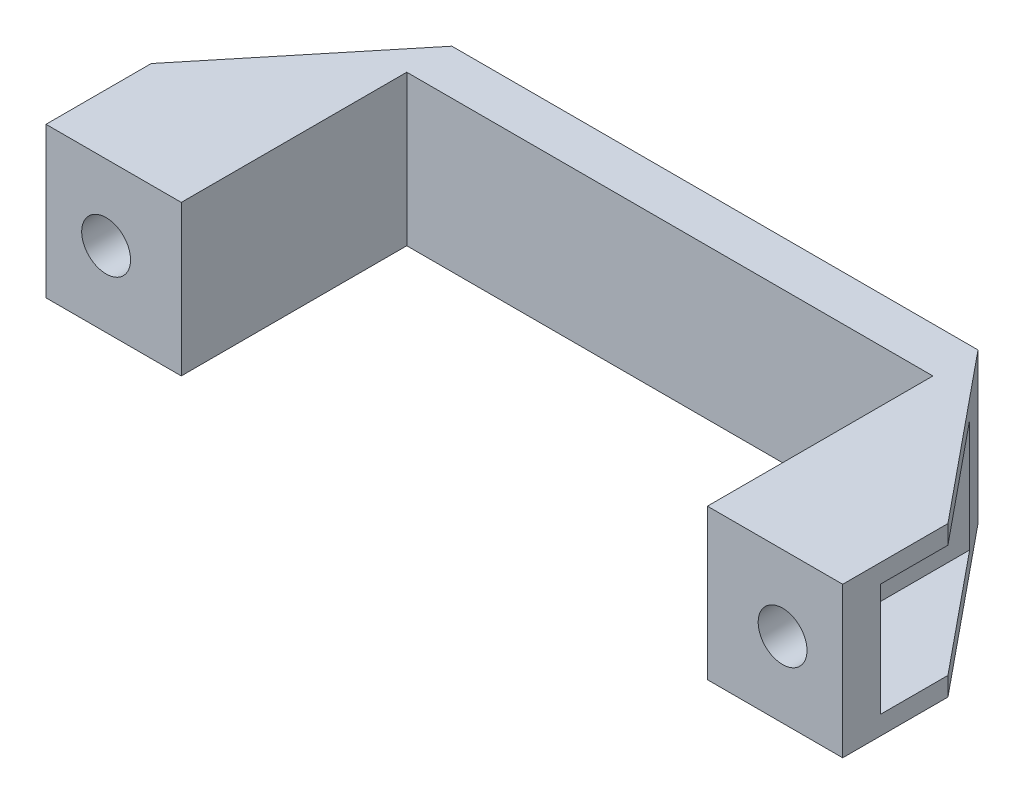
SolidWorks part; units mm, degrees
material "6061 合金"
ref_plane "前视基准面" through (0, 0, 0) normal (0, 0, 1) x (1, 0, 0)
ref_plane "上视基准面" through (0, 0, 0) normal (0, 1, 0) x (1, 0, 0)
ref_plane "右视基准面" through (0, 0, 0) normal (1, 0, 0) x (0, 0, -1)
ref_axis "X" through (88.99, 0, 0) along (-1, 0, 0)
ref_axis "Y" through (0, 66, 0) along (0, -1, 0)
ref_axis "Z" through (0, 0, 55) along (0, 0, -1)
sketch "草图1" plane through (0, 0, 0) normal (0, 1, 0) x (1, 0, 0)
  line L0 (-35, -18) -> (-35, 12)
  line L1 (-53, -18) -> (53, -18)
  line L2 (-53, -18) -> (-53, 18)
  line L3 (-53, 18) -> (53, 18)
  line L4 (53, -18) -> (53, 18)
  line L5 (-53, -18) -> (53, 18) construction
  line L6 (-53, 18) -> (53, -18) construction
  line L7 (-35, 12) -> (35, 12)
  line L8 (0, 12) -> (0, -18) construction
  line L9 (-53, -4) -> (-35, 18)
  line L10 (35, -18) -> (35, 12)
  line L11 (53, -4) -> (35, 18)
  point P0 (0, 0)
  dimension "D1" = 106
  dimension "D2" = 36
  dimension "D3" = 70
  dimension "D4" = 6
  dimension "D5" = 14
extrude "凸台-拉伸1" add sketch "草图1" along normal mid plane 20 contours L4 L11 L3 L9 L2 L1 L0 L7 L10 region at (-44, 0, 16.8805)
sketch "草图2" plane through (0, 0, 18) normal (0, 0, 1) x (1, 0, 0)
  line L0 (0, 0) -> (-45, 0) construction
  line L1 (0, 0) -> (0, -10) construction
  line L2 (-35, -10) -> (35, -10) construction
  circle A0 centre (-45, 0) radius 3.25
  circle A1 centre (45, 0) radius 3.25
  dimension "D2" = 6.5
  dimension "D1" = 45
extrude "切除-拉伸1" cut sketch "草图2" against normal through all
sketch "草图4" plane through (0, 0, 0) normal (0, 1, 0) x (1, 0, 0)
  line L0 (53, -4) -> (35, 18) construction
  line L1 (40, 11.8889) -> (53, 11.8889)
  line L2 (40, 11.8889) -> (40, -13)
  line L3 (40, -13) -> (53, -13)
  line L4 (53, 11.8889) -> (53, -13)
  line L5 (53, -18) -> (53, -4) construction
  line L6 (35, -18) -> (53, -18) construction
  line L7 (35, -18) -> (35, 12) construction
  line L8 (0, 0) -> (0, -13.0269) construction
  line L9 (-53, 11.8889) -> (-53, -13)
  line L10 (-40, -13) -> (-53, -13)
  line L11 (-40, 11.8889) -> (-40, -13)
  line L12 (-40, 11.8889) -> (-53, 11.8889)
  dimension "D1" = 5
  dimension "D2" = 5
extrude "切除-拉伸2" cut sketch "草图4" against normal mid plane 15
